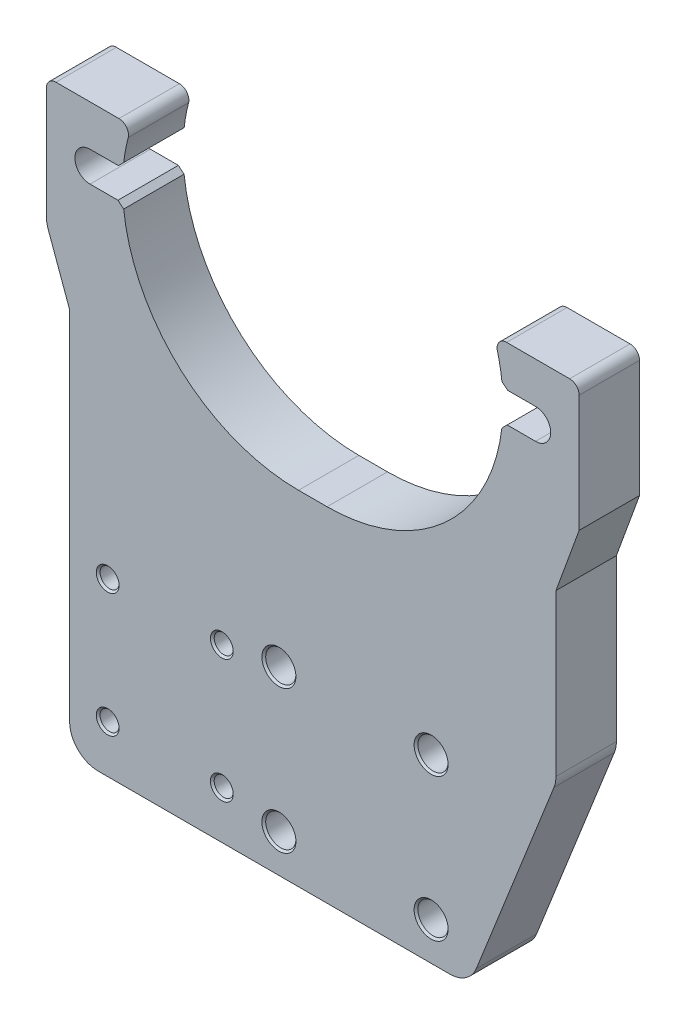
SolidWorks part; units mm, degrees
ref_plane "Front Plane" through (0, 0, 0) normal (0, 0, 1) x (1, 0, 0)
ref_plane "Top Plane" through (0, 0, 0) normal (0, 1, 0) x (1, 0, 0)
ref_plane "Right Plane" through (0, 0, 0) normal (1, 0, 0) x (0, 0, -1)
sketch "Sketch1" plane through (0, 0, 0) normal (0, 0, 1) x (1, 0, 0)
  line L0 (-8, 7.5) -> (8, 7.5) construction
  line L5 (-26, 6.5) -> (-14, 6.5) construction
  line L7 (-8, -7.5) -> (8, -7.5) construction
  line L8 (-8, -7.5) -> (-8, 7.5) construction
  line L9 (-8, 7.5) -> (8, 7.5) construction
  line L10 (8, -7.5) -> (8, 7.5) construction
  line L11 (-8, -7.5) -> (8, 7.5) construction
  line L12 (-8, 7.5) -> (8, -7.5) construction
  line L13 (-8, 7.5) -> (-8, -7.5) construction
  line L14 (-26, -6.5) -> (-14, -6.5) construction
  line L15 (-26, -6.5) -> (-26, 6.5) construction
  line L16 (-26, 6.5) -> (-14, 6.5) construction
  line L17 (-14, -6.5) -> (-14, 6.5) construction
  line L18 (-26, -6.5) -> (-14, 6.5) construction
  line L19 (-26, 6.5) -> (-14, -6.5) construction
  line L20 (0, 0) -> (-20, 0) construction
  line L21 (-6.4375, 59.6343) -> (-6.4375, -58.2445) construction
  line L22 (-30, -11.5) -> (12, -11.5)
  line L23 (-30, -11.5) -> (-30, 11.5)
  line L24 (-30, 11.5) -> (12, 11.5)
  line L25 (12, -11.5) -> (12, 11.5)
  line L26 (-30, -11.5) -> (12, 11.5) construction
  line L27 (-30, 11.5) -> (12, -11.5) construction
  line L28 (-11.5, -15) -> (-28.5, -15) construction
  line L29 (-11.5, -15) -> (-11.5, 15) construction
  line L30 (-11.5, 15) -> (-28.5, 15) construction
  line L31 (-28.5, -15) -> (-28.5, 15) construction
  line L32 (-11.5, -15) -> (-28.5, 15) construction
  line L33 (-11.5, 15) -> (-28.5, -15) construction
  line L34 (-59, 15) -> (41, 15) construction
  line L35 (-59, 15) -> (-59, 24) construction
  line L36 (-59, 24) -> (41, 24) construction
  line L37 (41, 15) -> (41, 24) construction
  line L38 (-59, -10) -> (41, -10) construction
  line L39 (-59, -10) -> (-59, 10) construction
  line L40 (-59, 10) -> (41, 10) construction
  line L41 (41, -10) -> (41, 10) construction
  line L42 (-59, -10) -> (41, 10) construction
  line L43 (-59, 10) -> (41, -10) construction
  line L44 (-30, -11.5) -> (12, -11.5)
  line L45 (-30, -11.5) -> (-30, 29)
  line L46 (-30, 29) -> (12, 29)
  line L47 (12, -11.5) -> (12, 29)
  line L48 (-4.4375, 43.1) -> (17.4825, 43.1) construction
  line L49 (-4.4375, 43.1) -> (-26.3575, 43.1) construction
  line L50 (-24.8575, 43.1) -> (-27.8575, 43.1) construction
  line L51 (-24.8575, 41.5125) -> (-27.8575, 41.5125)
  line L52 (-24.8575, 44.6875) -> (-27.8575, 44.6875)
  line L53 (15.9825, 43.1) -> (18.9825, 43.1) construction
  line L54 (15.9825, 44.6875) -> (18.9825, 44.6875)
  line L55 (15.9825, 41.5125) -> (18.9825, 41.5125)
  line L56 (-24.8575, 44.6875) -> (-22.8693, 44.6875)
  line L57 (-24.8575, 41.5125) -> (-22.8693, 41.5125)
  line L58 (15.9825, 41.5125) -> (13.9943, 41.5125)
  line L59 (15.9825, 44.6875) -> (13.9943, 44.6875)
  line L60 (-4.4375, 43.1) -> (-4.4375, 61.6) construction
  line L61 (12, -11.5) -> (21.125, 11.5)
  line L62 (21.125, 11.5) -> (21.125, 29)
  line L63 (21.125, 29) -> (12, 29)
  line L64 (21.125, 29) -> (28.4044, 49)
  line L65 (-30, 29) -> (-37.2794, 49)
  line L66 (-37.2794, 49) -> (28.4044, 49)
  line L67 (-5.9375, 43.1) -> (-2.9375, 43.1) construction
  line L68 (-5.9375, 61.6) -> (-2.9375, 61.6)
  line L69 (-5.9375, 24.6) -> (-2.9375, 24.6)
  line L70 (23.5625, 35.697) -> (23.5625, 49)
  line L71 (-32.4375, 35.697) -> (-32.4375, 49)
  circle A0 centre (-8, 7.5) radius 1.5875
  circle A2 centre (8, 7.5) radius 1.5875
  circle A3 centre (8, -7.5) radius 1.5875
  circle A4 centre (-8, -7.5) radius 1.5875
  circle A5 centre (-26, 6.5) radius 1
  circle A6 centre (-14, 6.5) radius 1
  circle A7 centre (-14, -6.5) radius 1
  circle A8 centre (-26, -6.5) radius 1
  circle A9 centre (-8, 7.5) radius 2.9 construction
  circle A10 centre (-14, 6.5) radius 2
  circle A11 centre (-26, 6.5) radius 2
  circle A12 centre (-26, -6.5) radius 2
  circle A13 centre (-14, -6.5) radius 2
  circle A14 centre (-4.4375, 43.1) radius 2 construction
  circle A15 centre (-4.4375, 43.1) radius 8 construction
  circle A16 centre (-4.4375, 43.1) radius 18.5
  circle A17 centre (17.4825, 43.1) radius 1.5875 construction
  circle A18 centre (-26.3575, 43.1) radius 1.5875 construction
  arc A19 (-24.8575, 41.5125) -> (-24.8575, 44.6875) centre (-24.8575, 43.1) ccw
  arc A20 (-27.8575, 44.6875) -> (-27.8575, 41.5125) centre (-27.8575, 43.1) ccw
  arc A21 (15.9825, 44.6875) -> (15.9825, 41.5125) centre (15.9825, 43.1) ccw
  arc A22 (18.9825, 41.5125) -> (18.9825, 44.6875) centre (18.9825, 43.1) ccw
  arc A23 (-5.9375, 61.6) -> (-5.9375, 24.6) centre (-5.9375, 43.1) ccw
  arc A24 (-2.9375, 24.6) -> (-2.9375, 61.6) centre (-2.9375, 43.1) ccw
  point P0 (0, 0)
  point P1 (-20, 0)
  point P4 (-9, 0)
  point P6 (0, 0)
  point P46 (-9, 15)
  point P47 (-9, 0)
  point P70 (-26.3575, 43.1)
  point P77 (17.4825, 43.1)
  point P97 (-4.4375, 43.1)
  dimension "D5" = 3.175
  dimension "D6" = 2
  dimension "D18" = 5.8
  dimension "D27" = 4
  dimension "D29" = 4
  dimension "D30" = 16
  dimension "D31" = 37
  dimension "D33" = 3.175
  dimension "D35" = 1.5875
  dimension "D40" = 18.5
  dimension "D1" = 15
  dimension "D2" = 16
  dimension "D3" = 13
  dimension "D4" = 12
  dimension "D9" = 16
  dimension "D10" = 15
  dimension "D13" = 12
  dimension "D14" = 20
  dimension "D15" = 23
  dimension "D16" = 4
  dimension "D17" = 4
  dimension "D19" = 17
  dimension "D20" = 30
  dimension "D21" = 9
  dimension "D22" = 100
  dimension "D23" = 20
  dimension "D24" = 100
  dimension "D25" = 15
  dimension "D26" = 40.5
  dimension "D28" = 13.5625
  dimension "D32" = 21.92
  dimension "D34" = 19.1
  dimension "D36" = 3
  dimension "D37" = 9.125
  dimension "D38" = 110
  dimension "D39" = 20
  dimension "D41" = 3
  dimension "D42" = 28
  dimension "D7" = 2
  dimension "D8" = 2
  dimension "D11" = 2
  dimension "D12" = 2
extrude "Boss-Extrude1" add sketch "Sketch1" along normal blind 6.35 contours A20 L52 L56 A16 L66 L65 L46 L57 L51 | A22 L55 L58 A16 L46 L63 L64 L66 L59 L54 | L62 L63 L47 L25 L61 | A16 L46 L45 L24 L47 | L22 L25 L24 L23 A13 A12 A11 A10 A4 A3 A2 A0 | A10 A6 | A11 A5 | A12 A8 | A13 A7 region at (-8.697, 0, 0) region at (15.9594, 13.7399, 0) region at (-9.5992, 19.3431, 0) region at (-27.3919, 37.9969, 0) region at (18.5169, 37.9969, 0) region at (-15.9434, 6.5, 0) region at (-27.9434, 6.5, 0) region at (-27.9434, -6.5, 0) region at (-15.9434, -6.5, 0)
extrude "Cut-Extrude1" cut sketch "Sketch1<3>" along normal blind 2.2 contours A10 A6 | A11 A5 | A12 A8 | A13 A7 | A13 region at (-15.9434, 6.5, 0) region at (-27.9434, 6.5, 0) region at (-27.9434, -6.5, 0) region at (-15.9434, -6.5, 0)
sketch "Sketch1<3>" plane through (0, 0, 0) normal (0, 0, 1) x (1, 0, 0) same geometry as "Sketch1"
chamfer "Chamfer1" distance 0.2 angle 45 16 edges at (-24, 6.5, 0) (-24, -6.5, 0) (-12, -6.5, 0) (-12, 6.5, 0) (-6.4125, -7.5, 0) (9.5875, -7.5, 0) (9.5875, 7.5, 0) (-6.4125, 7.5, 0) (-25, -6.5, 6.35) (-25, 6.5, 6.35) (-13, 6.5, 6.35) (-13, -6.5, 6.35) (-6.4125, -7.5, 6.35) (9.5875, -7.5, 6.35) (9.5875, 7.5, 6.35) (-6.4125, 7.5, 6.35)
fillet "Fillet1" radius 3 4 edges at (-30, -11.5, 3.175) (12, -11.5, 3.175) (21.125, 11.5, 3.175) (-32.4375, 35.697, 3.175)
fillet "Fillet2" radius 1 4 edges at (14.5965, 49, 3.175) (-23.4715, 49, 3.175) (23.5625, 49, 3.175) (-32.4375, 49, 3.175)
chamfer "Chamfer2" distance 0.5 angle 45 4 edges at (-24.3693, 41.5125, 3.175) (-24.3693, 44.6875, 3.175) (15.4943, 44.6875, 3.175) (15.4943, 41.5125, 3.175) first distance on face at (-16.7993, 31.2625, 3.175) first distance on face at (-26.1134, 44.6875, 3.175) first distance on face at (15.2638, 46.2236, 3.175) first distance on face at (17.2384, 41.5125, 3.175)
